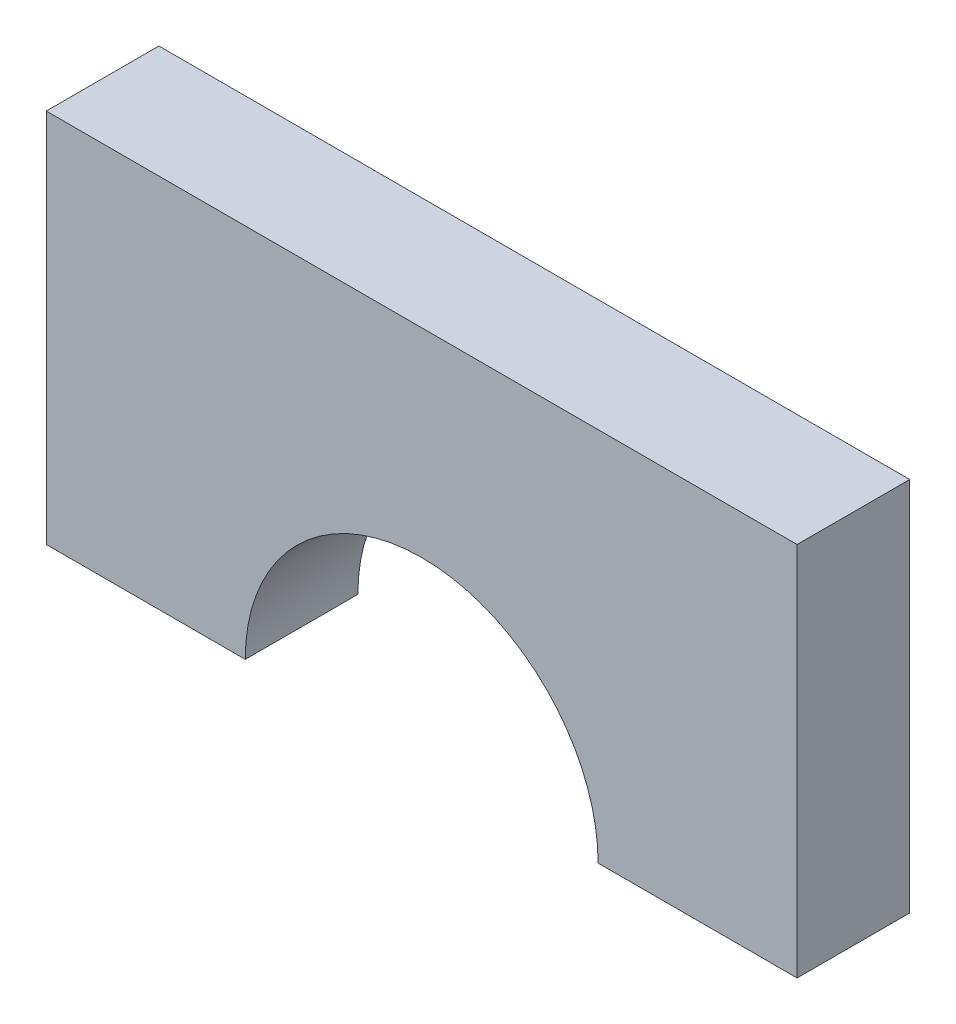
SolidWorks part; units mm, degrees
ref_plane "Plan de face" through (0, 0, 0) normal (0, 0, 1) x (1, 0, 0)
ref_plane "Plan de dessus" through (0, 0, 0) normal (0, 1, 0) x (1, 0, 0)
ref_plane "Plan de droite" through (0, 0, 0) normal (1, 0, 0) x (0, 0, -1)
sketch "Esquisse1" plane through (0, 0, 0) normal (0, 0, 1) x (1, 0, 0)
  line L0 (-76.1592, 33.8812) -> (23.8408, 33.8812)
  line L1 (-76.1592, 33.8812) -> (-76.1592, -16.1188)
  line L2 (-76.1592, -16.1188) -> (23.8408, -16.1188)
  line L3 (23.8408, 33.8812) -> (23.8408, -16.1188)
  arc A0 (-2.6592, -16.1188) -> (-49.6592, -16.1188) centre (-26.1592, -16.1188) ccw
  dimension "D1" = 23.5
extrude "Boss.-Extru.1" add sketch "Esquisse1" along normal blind 15 contours A0 L2 L3 L0 L1 region at (-26.1592, 12.0354, 0)
